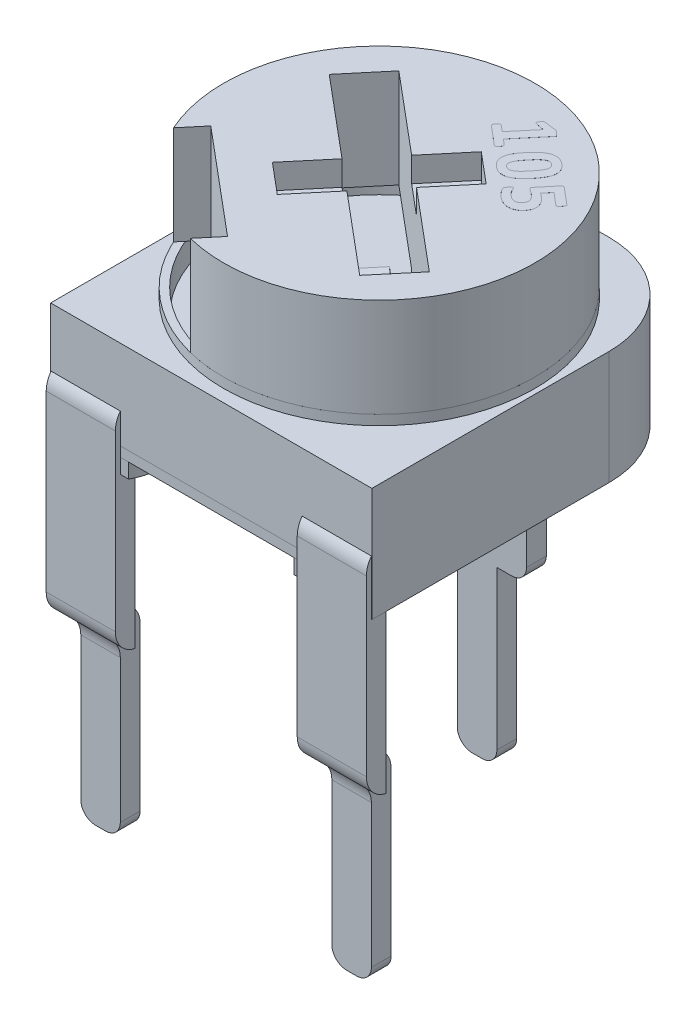
SolidWorks part; units mm, degrees
material "ABS"
ref_plane "Front Plane" through (0, 0, 0) normal (0, 0, 1) x (1, 0, 0)
ref_plane "Top Plane" through (0, 0, 0) normal (0, 1, 0) x (1, 0, 0)
ref_plane "Right Plane" through (0, 0, 0) normal (1, 0, 0) x (0, 0, -1)
sketch "Sketch1" plane through (0, 0, 0) normal (0, 1, 0) x (1, 0, 0)
  line L0 (0, 3.15) -> (0, -3.15) construction
  line L1 (0, 3.15) -> (0, 3.4) construction
  line L2 (0, -3.15) -> (0, -3.4) construction
  line L3 (-3.15, 0) -> (3.15, 0) construction
  line L4 (3.15, 0) -> (3.25, 0) construction
  line L5 (-3.15, 0) -> (-3.25, 0) construction
  line L6 (-3.25, -3.4) -> (3.25, -3.4)
  line L7 (-3.25, -3.4) -> (-3.25, 3.4)
  line L8 (-3.25, 3.4) -> (3.25, 3.4)
  line L9 (3.25, 3.4) -> (3.25, -3.4)
  circle A0 centre (0, 0) radius 3.15 construction
  dimension "D1" = 6.3
  dimension "D2" = 6.8
  dimension "D3" = 6.5
extrude "Boss-Extrude1" add sketch "Sketch1" along normal blind 2.3
sketch "Sketch2" plane through (0, 2.3, 0) normal (0, 1, 0) x (1, 0, 0)
  circle A0 centre (0, 0) radius 3.15 construction
  circle A1 centre (0, 0) radius 3.15
extrude "Boss-Extrude2" add sketch "Sketch2" along normal blind 0.2
fillet "Fillet1" radius 2 2 edges at (3.25, 1.15, -3.4) (-3.25, 1.15, -3.4)
sketch "Sketch3" plane through (0, 0, 0) normal (0, -1, 0) x (1, 0, 0)
  line L0 (0, 0) -> (0, -2.5) construction
  line L1 (-1.75, -2.5) -> (1.75, -2.5)
  line L6 (-2.25, -2) -> (-2.25, 2)
  line L7 (2.25, -2) -> (2.25, 2)
  line L8 (-2.25, 2) -> (-3, 2)
  line L9 (-3, 2) -> (-3, 3.4)
  line L10 (-3.25, 3.4) -> (3.25, 3.4) construction
  line L11 (2.25, 2) -> (3, 2)
  line L12 (3, 2) -> (3, 3.4)
  line L13 (3, 3.4) -> (-3, 3.4)
  line L14 (0, 0) -> (0, 3.4) construction
  arc A0 (-1.75, -2.5) -> (-2.25, -2) centre (-1.75, -2) cw
  arc A1 (1.75, -2.5) -> (2.25, -2) centre (1.75, -2) ccw
  point P20 (2.25, -2.5)
  dimension "D6" = 0.5
  dimension "D1" = 4.5
  dimension "D2" = 2.5
  dimension "D3" = 4.5
  dimension "D4" = 1.4
  dimension "D5" = 6
extrude "Cut-Extrude1" cut sketch "Sketch3" against normal blind 0.5
sketch "Sketch4" plane through (0, 0.5, 0) normal (0, -1, 0) x (1, 0, 0)
  line L8 (-3, 2) -> (-2.25, 2)
  line L9 (-2.25, 2) -> (-2.25, -2)
  line L10 (-1.75, -2.5) -> (1.75, -2.5)
  line L11 (2.25, -2) -> (2.25, 2)
  line L12 (2.25, 2) -> (3, 2)
  line L13 (3, 2) -> (3, 3.4)
  line L14 (3, 3.4) -> (-3, 3.4)
  line L15 (-3, 3.4) -> (-3, 2)
  line L16 (-3, 2) -> (-2.25, 2)
  line L17 (-2.25, 2) -> (-2.25, -2)
  line L18 (-1.75, -2.5) -> (1.75, -2.5)
  line L19 (2.25, -2) -> (2.25, 2)
  line L20 (2.25, 2) -> (3, 2)
  line L21 (3, 2) -> (3, 3.4)
  line L22 (3, 3.4) -> (-3, 3.4)
  line L23 (-3, 3.4) -> (-3, 2)
  arc A2 (-2.25, -2) -> (-1.75, -2.5) centre (-1.75, -2) ccw
  arc A3 (1.75, -2.5) -> (2.25, -2) centre (1.75, -2) ccw
  arc A4 (-2.25, -2) -> (-1.75, -2.5) centre (-1.75, -2) ccw
  arc A5 (1.75, -2.5) -> (2.25, -2) centre (1.75, -2) ccw
  dimension "D1" = 0
extrude "Boss-Extrude3" add sketch "Sketch4" along normal blind 0.2 separate body
sketch "Sketch5" plane through (0, 0.3, 0) normal (0, -1, 0) x (1, 0, 0)
  line L0 (0, 3.4) -> (0, 2.9) construction
  line L1 (3, 3.4) -> (-3, 3.4) construction
  line L2 (0, 2.9) -> (0, -2.18) construction
  line L3 (-2.54, 2.9) -> (2.54, 2.9) construction
  circle A0 centre (2.54, 2.9) radius 1
  circle A1 centre (-2.54, 2.9) radius 1
  circle A2 centre (0, -2.18) radius 1
  dimension "D2" = 5.08
  dimension "D4" = 2
  dimension "D1" = 0.5
  dimension "D3" = 5.08
extrude "Boss-Extrude4" add sketch "Sketch5" along normal up to surface (0.3 mm away) up to face at (0, 0, 0.1228)
sketch "Sketch6" plane through (0, 0.3, 0) normal (0, 1, 0) x (1, 0, 0)
  line L0 (-3.25, -3.4) -> (-3.25, -1)
  line L1 (-3.25, 1.4) -> (-3.25, -3.4) construction
  line L2 (-3.25, -1) -> (-4.35, -1)
  line L3 (-4.35, -1) -> (-4.35, -4.5)
  line L4 (-4.35, -4.5) -> (4.35, -4.5)
  line L5 (4.35, -4.5) -> (4.35, -1)
  line L6 (4.35, -1) -> (3.25, -1)
  line L7 (3.25, -3.4) -> (3.25, 1.4) construction
  line L8 (-3.25, -3.4) -> (3.25, -3.4)
  line L9 (3.25, -3.4) -> (3.25, -1)
  line L10 (0, 0) -> (0, -3.4) construction
  line L11 (0, -3.4) -> (0, -4.5) construction
  dimension "D1" = 3.5
extrude "Cut-Extrude2" cut sketch "Sketch6" against normal up to surface (0.3 mm away) up to face at (0, 0, -0.817)
sketch "Sketch8" plane through (0, 0.3, 0) normal (0, -1, 0) x (1, 0, 0)
  line L1 (-0.4, -1.98) -> (0.4, -1.98)
  line L2 (-0.4, -1.98) -> (-0.4, -2.38)
  line L3 (-0.4, -2.38) -> (0.4, -2.38)
  line L4 (0.4, -1.98) -> (0.4, -2.38)
  line L5 (-0.4, -1.98) -> (0.4, -2.38) construction
  line L6 (-0.4, -2.38) -> (0.4, -1.98) construction
  line L7 (-2.94, 3.1) -> (-2.14, 3.1)
  line L8 (-2.94, 3.1) -> (-2.94, 2.7)
  line L9 (-2.94, 2.7) -> (-2.14, 2.7)
  line L10 (-2.14, 3.1) -> (-2.14, 2.7)
  line L11 (-2.94, 3.1) -> (-2.14, 2.7) construction
  line L12 (-2.94, 2.7) -> (-2.14, 3.1) construction
  line L13 (2.94, 3.1) -> (2.14, 3.1)
  line L14 (2.94, 3.1) -> (2.94, 2.7)
  line L15 (2.94, 2.7) -> (2.14, 2.7)
  line L16 (2.14, 3.1) -> (2.14, 2.7)
  line L17 (2.94, 3.1) -> (2.14, 2.7) construction
  line L18 (2.94, 2.7) -> (2.14, 3.1) construction
  point P0 (0, -2.18)
  point P5 (-2.54, 2.9)
  point P11 (2.54, 2.9)
  dimension "D1" = 0.4
  dimension "D2" = 0.8
extrude "Boss-Extrude5" add sketch "Sketch8" along normal blind 7
sketch "Sketch9" plane through (0, 0.3, 0) normal (0, -1, 0) x (1, 0, 0)
  line L4 (0, -1.98) -> (0, -2.38) construction
  line L5 (0.4, -1.98) -> (-0.4, -1.98) construction
  line L6 (-0.4, -2.38) -> (0.4, -2.38) construction
  line L8 (-1, -1.98) -> (1, -1.98)
  line L9 (-1, -1.98) -> (-1, -2.38)
  line L10 (-1, -2.38) -> (1, -2.38)
  line L11 (1, -1.98) -> (1, -2.38)
  line L12 (-1, -1.98) -> (1, -2.38) construction
  line L13 (-1, -2.38) -> (1, -1.98) construction
  point P14 (0, -2.18)
  dimension "D1" = 2
extrude "Boss-Extrude6" add sketch "Sketch9" along normal blind 3.5
sketch "Sketch10" plane through (0, 0.3, 0) normal (0, -1, 0) x (1, 0, 0)
  line L0 (-2.54, 3.1) -> (-2.54, 3.5) construction
  line L1 (-2.14, 3.1) -> (-2.94, 3.1) construction
  line L2 (2.54, 3.1) -> (2.54, 3.5) construction
  line L3 (2.94, 3.1) -> (2.14, 3.1) construction
  line L4 (-2.94, 3.1) -> (-2.94, 2.7) construction
  line L5 (-3.24, 3.5) -> (-1.84, 3.5)
  line L6 (-3.24, 3.5) -> (-3.24, 3.1)
  line L7 (-3.24, 3.1) -> (-1.84, 3.1)
  line L8 (-1.84, 3.5) -> (-1.84, 3.1)
  line L10 (1.84, 3.5) -> (3.24, 3.5)
  line L11 (1.84, 3.5) -> (1.84, 3.1)
  line L12 (1.84, 3.1) -> (3.24, 3.1)
  line L13 (3.24, 3.5) -> (3.24, 3.1)
  dimension "D1" = 1.4
extrude "Boss-Extrude7" add sketch "Sketch10" along normal blind 3.5 and the other way blind 1
fillet "Fillet2" radius 0.5 2 edges at (2.54, 1.3, 3.5) (-2.54, 1.3, 3.5)
sketch "Sketch11" plane through (0, 0, 0) normal (1, 0, 0) x (0, 0, -1)
  line L0 (-3.4, 0) -> (1.4, 0) construction
  line L1 (-3.1, -2.8) -> (-2.7, -2.8)
  line L2 (-3.1, -2.8) -> (-3.1, 0)
  line L3 (-3.1, 0) -> (-2.7, 0)
  line L4 (-2.7, -2.8) -> (-2.7, 0)
  line L5 (-2.7, -6.7) -> (-2.7, 0.3) construction
  line L6 (-3.1, -2.8) -> (-3.1, -3.2) construction
extrude "Cut-Extrude3" cut sketch "Sketch11" against normal through all both and the other way through all
fillet "Fillet3" radius 0.5 4 edges at (-2.54, -2.8, 3.1) (2.54, -2.8, 3.1) (-2.54, -3.2, 3.5) (2.54, -3.2, 3.5)
fillet "Fillet4" radius 0.5 4 edges at (2.54, -2.8, 2.7) (-2.54, -2.8, 2.7) (2.54, -3.2, 3.1) (-2.54, -3.2, 3.1)
fillet "Fillet5" radius 0.3 12 edges at (-1, -3.2, -2.18) (1, -3.2, -2.18) (-0.4, -6.7, -2.18) (0.4, -6.7, -2.18) (2.14, -6.7, 2.9) (2.94, -6.7, 2.9) (-2.94, -6.7, 2.9) (-2.14, -6.7, 2.9) (-2.14, -2.7551, 3.1) (-2.94, -2.7551, 3.1) (2.14, -2.7551, 3.1) (2.94, -2.7551, 3.1)
sketch "Sketch12" plane through (0, 0.3, 0) normal (0, -1, 0) x (1, 0, 0)
  circle A0 centre (0, 0) radius 2
  circle A1 centre (0, 0) radius 1.5
  dimension "D1" = 4
  dimension "D2" = 3
extrude "Boss-Extrude8" add sketch "Sketch12" along normal blind 0.15
sketch "Sketch15" plane through (0, 2.5, 0) normal (0, 1, 0) x (1, 0, 0)
  circle A0 centre (0, 0) radius 3
  dimension "D1" = 6
extrude "Cut-Extrude4" cut sketch "Sketch15" against normal blind 0.5
sketch "Sketch14" plane through (0, 2.5, 0) normal (0, 1, 0) x (1, 0, 0)
  circle A1 centre (0, 0) radius 3.15
  circle A2 centre (0, 0) radius 3.15
  dimension "D1" = 0
extrude "Boss-Extrude9" add sketch "Sketch14" along normal blind 2 separate body
sketch "Set Angle of Knob" plane through (0, 4.5, 0) normal (0, 1, 0) x (1, 0, 0)
  line L0 (0, 0) -> (0, -3.15) construction
  line L1 (-1.9151, 1.607) -> (1.9151, -1.607) construction
  line L2 (-1.5937, 1.99) -> (-2.2365, 1.2239)
  line L3 (2.2365, -1.2239) -> (1.5937, -1.99)
  line L4 (-1.5937, 1.99) -> (0.015, 0.6401)
  line L5 (-2.2365, 1.2239) -> (-0.6278, -0.1259)
  line L6 (0, 0) -> (-0.9642, -1.1491) construction
  line L7 (0, 0) -> (0.9642, 1.1491) construction
  line L8 (0.9642, 1.1491) -> (2.0248, 2.413) construction
  line L9 (1.2706, 0.892) -> (0.6578, 1.4062)
  line L10 (1.2706, 0.892) -> (0.6278, 0.1259)
  line L11 (0.6578, 1.4062) -> (0.015, 0.6401)
  line L12 (0.6278, 0.1259) -> (2.2365, -1.2239)
  line L13 (-1.2706, -0.892) -> (-0.6578, -1.4062)
  line L14 (-1.2706, -0.892) -> (-0.6278, -0.1259)
  line L15 (-0.6578, -1.4062) -> (-0.015, -0.6401)
  line L16 (-0.015, -0.6401) -> (1.5937, -1.99)
  line L17 (-0.9642, -1.1491) -> (-1.4784, -1.7619) construction
  line L18 (-2.5317, -0.8781) -> (-0.4251, -2.6457)
  line L19 (-2.5317, -0.8781) -> (-3.4959, -2.0271)
  line L20 (-0.4251, -2.6457) -> (-1.3893, -3.7948)
  line L21 (-3.4959, -2.0271) -> (-1.3893, -3.7948)
  line L22 (-0.6053, 0.8343) -> (0.9267, -0.4513) construction
  line L23 (-0.6053, 0.8343) -> (-0.9267, 0.4513) construction
  line L24 (-0.9267, 0.4513) -> (0.6053, -0.8343) construction
  line L25 (0.6053, -0.8343) -> (0.9267, -0.4513) construction
  circle A0 centre (0, 0) radius 3.15 construction
  circle A1 centre (0, 0) radius 3.15 construction
  point P32 (0.1607, 0.1915)
  dimension "D1" = 1
  dimension "D2" = 0.8
  dimension "D3" = 1.5
  dimension "D4" = 5
  dimension "D5" = 50
  dimension "D6" = 2.75
  dimension "D7" = 1.5
  dimension "D8" = 1.8
  dimension "D9" = 0.25
  dimension "D10" = 0.25
  dimension "D11" = 2
extrude "TURN KNOB" cut sketch "Set Angle of Knob" against normal blind 2.3
sketch "Sketch17" plane through (0, 2, 0) normal (0, 1, 0) x (1, 0, 0)
  line L0 (-1.2706, -0.892) -> (-0.6578, -1.4062)
  line L1 (-0.6578, -1.4062) -> (-0.015, -0.6401)
  line L2 (1.2706, 0.892) -> (0.6578, 1.4062)
  line L3 (0.6578, 1.4062) -> (0.015, 0.6401)
  line L4 (0.015, 0.6401) -> (0.6278, 0.1259)
  line L5 (-0.6278, -0.1259) -> (-0.015, -0.6401)
  line L6 (-0.6278, -0.1259) -> (-1.2706, -0.892)
  line L7 (0.6278, 0.1259) -> (1.2706, 0.892)
extrude "Boss-Extrude10" add sketch "Sketch17" along normal blind 2
sketch "Sketch20" plane through (0, 2, 0) normal (0, 1, 0) x (1, 0, 0)
  line L0 (-0.6053, 0.8343) -> (0.9267, -0.4513) construction
  line L1 (-0.6053, 0.8343) -> (0.9267, -0.4513)
  line L2 (-0.9267, 0.4513) -> (0.6053, -0.8343) construction
  line L3 (-0.9267, 0.4513) -> (0.6053, -0.8343)
  line L4 (-0.6053, 0.8343) -> (-0.9267, 0.4513) construction
  line L5 (-0.6053, 0.8343) -> (-0.9267, 0.4513)
  line L6 (0.6053, -0.8343) -> (0.9267, -0.4513) construction
  line L7 (0.6053, -0.8343) -> (0.9267, -0.4513)
extrude "Cut-Extrude6" cut sketch "Sketch20" against normal blind 0.5
fillet "Fillet6" radius 0.2 2 edges at (0.766, 2, 0.6428) (-0.766, 2, -0.6428)
sketch "Sketch18" plane through (0, 4.5, 0) normal (0, 1, 0) x (1, 0, 0)
  line L0 (0.9642, 1.1491) -> (1.0927, 1.3023) construction
  line L1 (1.2706, 0.892) -> (0.6578, 1.4062) construction
  line L2 (0.9642, 1.1491) -> (2.0248, 2.413) construction
  line L3 (-0.0563, 2.2665) -> (2.2418, 0.3381) construction
  text T0 "105" font "Calibri" height 0.9
  dimension "D1" = 0.2
  dimension "D2" = 3
extrude "Code Number" add sketch "Sketch18" along normal blind 0.001
